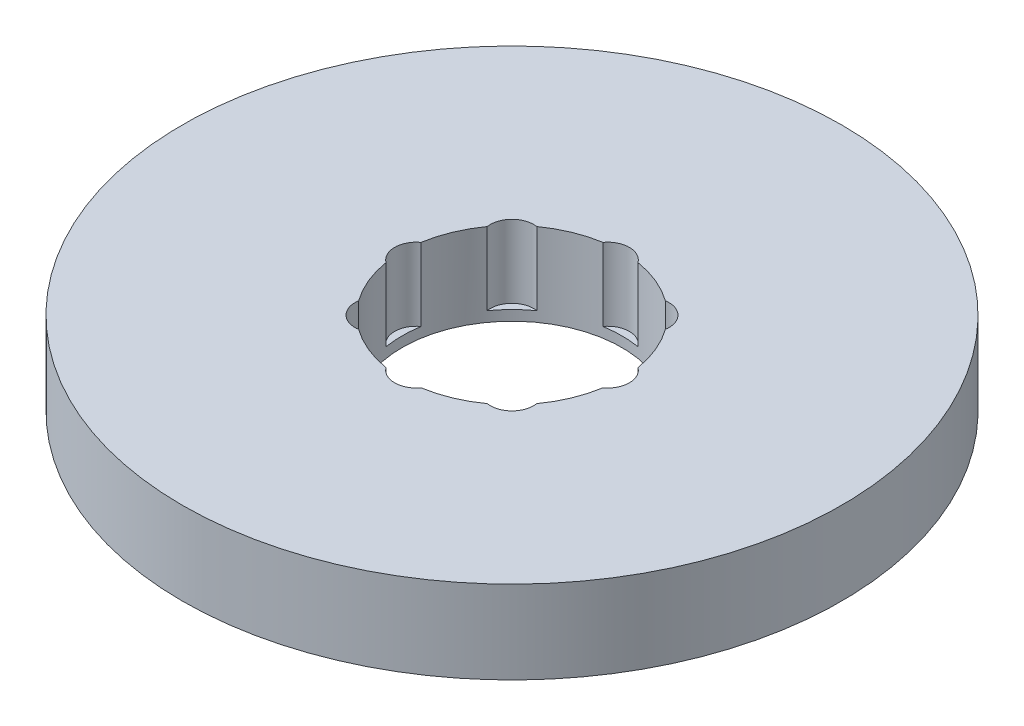
SolidWorks part; units mm, degrees
ref_plane "Front Plane" through (0, 0, 0) normal (0, 0, 1) x (1, 0, 0)
ref_plane "Top Plane" through (0, 0, 0) normal (0, 1, 0) x (1, 0, 0)
ref_plane "Right Plane" through (0, 0, 0) normal (1, 0, 0) x (0, 0, -1)
sketch "Sketch1" plane through (0, 0, 0) normal (0, 1, 0) x (1, 0, 0)
  circle A0 centre (0, 0) radius 67.5
  dimension "FLANGE_OD" = 135
extrude "Boss-Extrude1" add sketch "Sketch1" along normal blind 17
sketch "Sketch2" plane through (0, 0, 0) normal (0, 1, 0) x (1, 0, 0)
  circle A0 centre (0, 0) radius 22.5
  dimension "BORE_D" = 45
extrude "Cut-Extrude1" cut sketch "Sketch2" along normal through all
sketch "Sketch3" plane through (0, 17, 0) normal (0, 1, 0) x (1, 0, 0)
  circle A0 centre (0, 0) radius 19.5929 construction
  circle A1 centre (-19.5929, 0) radius 4.4429
  dimension "BOLT_D" = 8.8858
  dimension "BOLT_PCD" = 39.1857
extrude "Cut-Extrude2" cut sketch "Sketch3" against normal blind 14.9153
pattern_circular "CirPattern1" count 8 over 360 about axis through (0, 0, 0) along (0, 1, 0) of "Cut-Extrude2"
